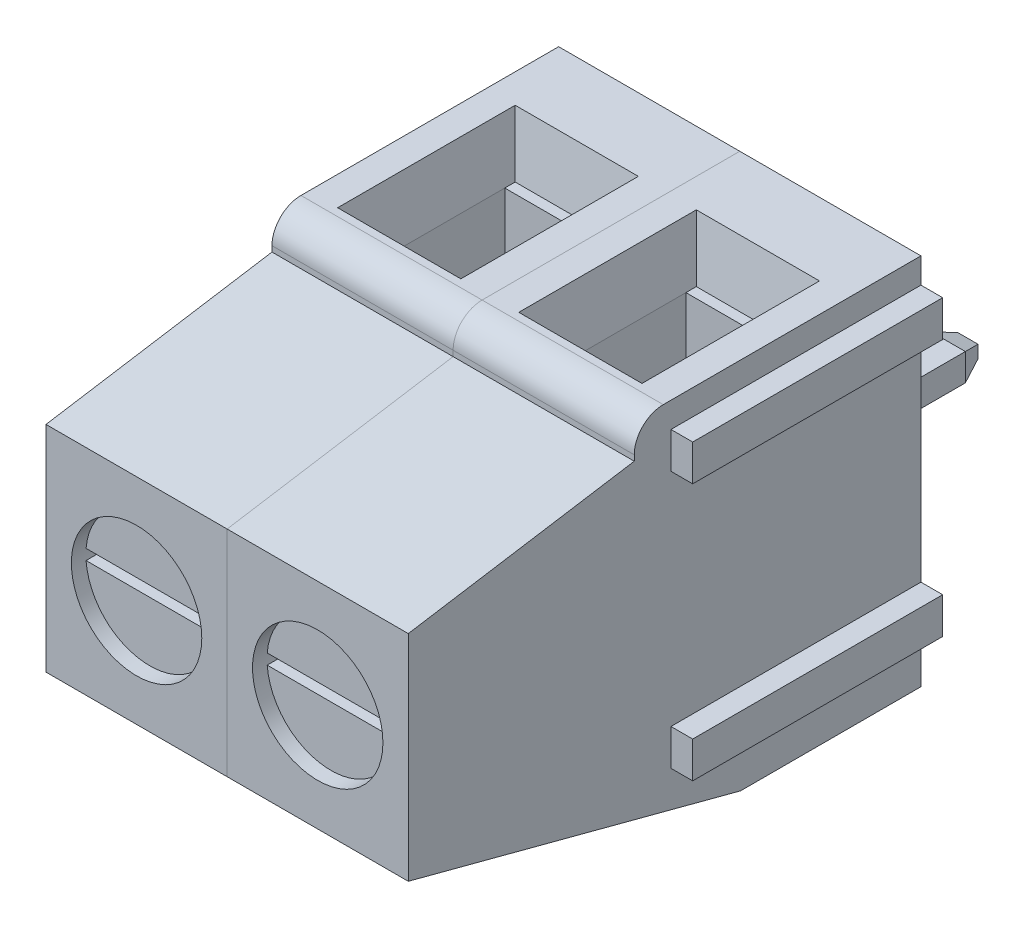
SolidWorks part; units mm, degrees
ref_plane "Спереди" through (0, 0, 0) normal (0, 0, 1) x (1, 0, 0)
ref_plane "Сверху" through (0, 0, 0) normal (0, 1, 0) x (1, 0, 0)
ref_plane "Справа" through (0, 0, 0) normal (1, 0, 0) x (0, 0, -1)
sketch "Эскиз3" plane through (0, 0, 0) normal (0, 0, 1) x (1, 0, 0)
  line L1 (-2.5, 5.3) -> (2.5, 5.3)
  line L2 (-2.5, 5.3) -> (-2.5, -5)
  line L3 (-2.5, -5) -> (2.5, -5)
  line L4 (2.5, 5.3) -> (2.5, -5)
  line L5 (-2.5, 5.3) -> (2.5, -5) construction
  line L6 (-2.5, -5) -> (2.5, 5.3) construction
  point P0 (0, 0.15)
  dimension "D1" = 10.3
  dimension "D2" = 5
  dimension "D3" = 5.3
extrude "Бобышка-Вытянуть2" add sketch "Эскиз3" along normal blind 14.15
sketch "Эскиз5" plane through (0, 0, 0) normal (0, 0, -1) x (-1, 0, 0)
  line L0 (-2.5, 5.3) -> (2.5, 5.3) construction
  line L1 (-1.5, 3.74) -> (1.5, 3.74)
  line L2 (-1.5, 3.74) -> (-1.5, -3.74)
  line L4 (1.5, 3.74) -> (1.5, -3.74)
  line L5 (-1.5, 3.74) -> (1.5, -3.74) construction
  line L6 (-1.5, -3.74) -> (1.5, 3.74) construction
  line L8 (2.5, -5) -> (-2.5, -5) construction
  line L10 (-1.5, -3.74) -> (-1.5, -4.14)
  line L11 (-1.5, -4.14) -> (1.5, -4.14)
  line L12 (1.5, -3.74) -> (1.5, -4.14)
  point P0 (0, 0)
  point P10 (0, -3.94)
  dimension "D1" = 3
  dimension "D2" = 1.56
  dimension "D3" = 0.86
extrude "Вырез-Вытянуть3" cut sketch "Эскиз5" against normal blind 6.9
sketch "Эскиз6" plane through (2.5, 0, 0) normal (1, 0, 0) x (0, 0, -1)
  line L0 (-80.2628, -91.3523) -> (-80.2628, -14.0189) construction
  line L1 (-4.9782, -5) -> (-14.15, -2.5764)
  line L2 (-14.15, -5) -> (0, -5) construction
  line L3 (-14.15, -5) -> (-14.15, 5.3) construction
  line L4 (-14.15, -2.5764) -> (-14.15, -5)
  line L5 (-14.15, -5) -> (-4.9782, -5)
  line L6 (-7.1129, 5.3) -> (-14.15, 5.3)
  line L7 (-14.15, 5.3) -> (0, 5.3) construction
  line L8 (-7.9129, 4.5) -> (-7.9129, 4.3474)
  line L9 (-7.9129, 4.3474) -> (-14.15, 3.3455)
  line L10 (-14.15, 3.3455) -> (-14.15, 5.3)
  arc A0 (-7.1129, 5.3) -> (-7.9129, 4.5) centre (-7.1129, 4.5) ccw
  point P20 (-7.9129, 5.3)
  dimension "D1" = 0.8
extrude "Вырез-Вытянуть4" cut sketch "Эскиз6" against normal through all
sketch "Эскиз7" plane through (0, 5.3, 0) normal (0, 1, 0) x (1, 0, 0)
  line L0 (2.5, -7.1129) -> (-2.5, 0) construction
  line L1 (2.5, 0) -> (-2.5, -7.1129) construction
  line L2 (-2.5, -7.1129) -> (-2.5, 0) construction
  line L3 (1.7, -6.9) -> (-1.7, -6.9)
  line L4 (1.7, -6.9) -> (1.7, -2)
  line L5 (1.7, -2) -> (-1.7, -2)
  line L6 (-1.7, -6.9) -> (-1.7, -2)
  line L7 (1.7, -6.9) -> (-1.7, -2) construction
  line L8 (1.7, -2) -> (-1.7, -6.9) construction
  line L10 (2.5, -7.1129) -> (2.5, 0) construction
  line L11 (2.5, 0) -> (-2.5, 0) construction
  point P8 (0, -4.45)
  dimension "D1" = 0.8
  dimension "D2" = 0.8
  dimension "D3" = 2
  dimension "D4" = 4.9
extrude "Вырез-Вытянуть5" cut sketch "Эскиз7" against normal blind 1.6 draft 10
sketch "Эскиз9" plane through (0, 5.3, 0) normal (0, 1, 0) x (1, 0, 0)
  line L0 (-1.7, -6.9) -> (-2.5, -6.9)
  line L1 (-2.5, -7.1129) -> (-2.5, 0) construction
  point P6 (-2.5, -6.9)
sketch "Эскиз10" plane through (-2.5, 0, 0) normal (-1, 0, 0) x (0, 0, 1)
  line L0 (6.9, 5.3) -> (5.5574, 3.7)
  line L1 (5.5574, 3.7) -> (6.9, 3.7)
  line L2 (6.9, 3.7) -> (6.9, 5.3)
  dimension "D1" = 1.6
  dimension "D2" = 40
extrude "Бобышка-Вытянуть3" add sketch "Эскиз10" against normal blind 4.6
sketch "Эскиз11" plane through (0, 0, 0) normal (0, 0, 1) x (1, 0, 0)
  line L0 (-2.5, -5) -> (2.5, -5) construction
  line L1 (-1, -3.7) -> (1, -3.7)
  line L2 (-1, -3.7) -> (-1, -5)
  line L3 (-1, -5) -> (1, -5)
  line L4 (1, -3.7) -> (1, -5)
  line L5 (-1, -3.7) -> (1, -5) construction
  line L6 (-1, -5) -> (1, -3.7) construction
  line L7 (0, 0) -> (0, -5) construction
  point P0 (0, -4.35)
  dimension "D1" = 2
  dimension "D2" = 1.3
extrude "Вырез-Вытянуть6" cut sketch "Эскиз11" along normal through all from offset 5
sketch "Эскиз13" plane through (-1, 0, 0) normal (1, 0, 0) x (0, 0, -1)
  line L0 (-6.9, -3.7) -> (-6.99, -4.2064)
  line L1 (-6.99, -4.2064) -> (-5, -4.3475)
  line L2 (-5, -4.14) -> (-5, -4.9942) construction
  line L3 (-5, -4.3475) -> (-5, -4.14)
  line L4 (-5, -4.14) -> (-6.9, -3.7)
extrude "Бобышка-Вытянуть6" add sketch "Эскиз13" against normal up to surface (0.5 mm away) up to face at (-1.5, 1.1, 4.1581)
sketch "Эскиз14" plane through (1, 0, 0) normal (-1, 0, 0) x (0, 0, 1)
  line L0 (6.9, -3.7) -> (5, -4.14)
  line L1 (6.9, -4.14) -> (6.9, -3.7) construction
  line L2 (9.8979, -3.7) -> (6.9, -3.7) construction
  line L3 (5, -4.14) -> (5, -4.475)
  line L4 (5, -4.9942) -> (5, -4.14) construction
  line L5 (5, -4.475) -> (7.0407, -4.3075)
  line L6 (7.0407, -4.3075) -> (6.9, -3.7)
extrude "Бобышка-Вытянуть7" add sketch "Эскиз14" against normal up to surface (0.5 mm away) up to face at (1.5, 1.1, 4.1581)
sketch "Эскиз15" plane through (0, 0, 14.15) normal (0, 0, 1) x (1, 0, 0)
  line L1 (2.5, -2.5764) -> (-2.5, -2.5764) construction
  line L2 (2.5, -2.5764) -> (2.5, 3.3455) construction
  line L3 (2.5, 3.3455) -> (-2.5, 3.3455) construction
  line L4 (-2.5, -2.5764) -> (-2.5, 3.3455) construction
  line L5 (2.5, -2.5764) -> (-2.5, 3.3455) construction
  line L6 (2.5, 3.3455) -> (-2.5, -2.5764) construction
  circle A0 centre (0, 0.3846) radius 1.8
  point P4 (0, 0.3846)
extrude "Вырез-Вытянуть7" cut sketch "Эскиз15" against normal blind 1.5
sketch "Эскиз16" plane through (0, 0, 12.65) normal (0, 0, 1) x (1, 0, 0)
  circle A0 centre (0, 0.3846) radius 1.75
extrude "Бобышка-Вытянуть8" add sketch "Эскиз16" along normal blind 0.5 separate body
sketch "Эскиз17" plane through (0, 0, 13.15) normal (0, 0, 1) x (1, 0, 0)
  line L1 (1.7445, 0.5356) -> (-1.8107, 0.5356)
  line L3 (1.7445, 0.2445) -> (-1.8107, 0.2445)
  arc A0 (1.7445, 0.5356) -> (-1.8107, 0.5356) centre (-0.0331, 0.39) ccw
  arc A1 (-1.8107, 0.2445) -> (1.7445, 0.2445) centre (-0.0331, 0.39) ccw
extrude "Бобышка-Вытянуть9" add sketch "Эскиз17" along normal blind 0.6
sketch "Эскиз18" plane through (0, 0, 0) normal (0, 0, -1) x (-1, 0, 0)
  line L1 (-2.5, 4.6) -> (-3.1, 4.6)
  line L2 (-2.5, 4.6) -> (-2.5, 3.6)
  line L3 (-2.5, 3.6) -> (-3.1, 3.6)
  line L4 (-3.1, 4.6) -> (-3.1, 3.6)
  line L5 (-2.5, 4.6) -> (-3.1, 3.6) construction
  line L6 (-2.5, 3.6) -> (-3.1, 4.6) construction
  line L7 (-2.5, 5.3) -> (2.5, 5.3) construction
  line L9 (-2.5, -3.5) -> (-3.1, -3.5)
  line L10 (-2.5, -3.5) -> (-2.5, -2.5)
  line L11 (-2.5, -2.5) -> (-3.1, -2.5)
  line L12 (-3.1, -3.5) -> (-3.1, -2.5)
  line L13 (-2.5, -3.5) -> (-3.1, -2.5) construction
  line L14 (-2.5, -2.5) -> (-3.1, -3.5) construction
  line L15 (2.5, -5) -> (-2.5, -5) construction
  point P4 (-2.8, 4.1)
  point P12 (-2.8, -3)
  dimension "D1" = 1
  dimension "D2" = 0.6
  dimension "D3" = 0.7
  dimension "D4" = 1
  dimension "D5" = 0.6
  dimension "D6" = 1.5
extrude "Бобышка-Вытянуть10" add sketch "Эскиз18" against normal blind 6.9
sketch "Эскиз19" plane through (0, 0, 0) normal (0, 0, -1) x (-1, 0, 0)
  line L0 (2.5, 5.3) -> (2.5, -5) construction
  line L1 (2.5, 4.6) -> (1.9, 4.6)
  line L2 (2.5, 4.6) -> (2.5, 3.6)
  line L3 (2.5, 3.6) -> (1.9, 3.6)
  line L4 (1.9, 4.6) -> (1.9, 3.6)
  line L5 (2.5, 4.6) -> (1.9, 3.6) construction
  line L6 (2.5, 3.6) -> (1.9, 4.6) construction
  line L7 (2.5, -5) -> (-2.5, -5) construction
  line L8 (2.5, -2.5) -> (1.9, -2.5)
  line L9 (2.5, -2.5) -> (2.5, -3.5)
  line L10 (2.5, -3.5) -> (1.9, -3.5)
  line L11 (1.9, -2.5) -> (1.9, -3.5)
  line L12 (2.5, -2.5) -> (1.9, -3.5) construction
  line L13 (2.5, -3.5) -> (1.9, -2.5) construction
  point P4 (2.2, 4.1)
  point P11 (2.2, -3)
  dimension "D1" = 0.6
  dimension "D2" = 0.6
  dimension "D3" = 1
  dimension "D4" = 1
  dimension "D5" = 1.5
extrude "Вырез-Вытянуть8" cut sketch "Эскиз19" against normal blind 6.9
sketch "Эскиз20" plane through (1.5, 0, 0) normal (-1, 0, 0) x (0, 0, 1)
  line L0 (6.9, -3.7) -> (0.8163, -3.7)
  line L1 (0.8163, -3.7) -> (0.8163, 0.4782)
  line L2 (0.8163, 0.4782) -> (1.1919, 0.4782)
  line L3 (1.1919, 0.4782) -> (1.1919, -3.3823)
  line L4 (1.1919, -3.3823) -> (7.0251, -3.3823)
  line L5 (7.0251, -3.3823) -> (6.9, -3.7)
extrude "Бобышка-Вытянуть11" add sketch "Эскиз20" along normal up to surface (3 mm away) separate body up to face at (-1.5, 0.4143, 4.2783)
sketch "Эскиз21" plane through (0, 0, 0.8163) normal (0, 0, -1) x (-1, 0, 0)
  line L0 (1.2161, -3.0918) -> (1.5, -3.0918)
  line L2 (1.2161, 0.4782) -> (1.2161, -3.0918)
  line L4 (-1.2161, 0.4782) -> (-1.2161, -3.0918)
  line L7 (1.5, 0.4782) -> (1.5, -3.7) construction
  line L8 (1.5, -3.0918) -> (1.5, 0.4782)
  line L9 (1.5, 0.4782) -> (1.2161, 0.4782)
  line L10 (1.5, 0.4782) -> (-1.5, 0.4782) construction
  line L11 (-1.5, 0.4782) -> (-1.2161, 0.4782)
  line L12 (-1.5, 0.4782) -> (-1.5, -3.0918)
  line L13 (-1.5, -3.0918) -> (-1.2161, -3.0918)
  point P0 (0, 0)
extrude "Вырез-Вытянуть9" cut sketch "Эскиз21" against normal blind 1.9
sketch "Эскиз22" plane through (0, 3.74, 0) normal (0, -1, 0) x (-1, 0, 0)
  line L0 (-1.5, -5.591) -> (-1.5, 0) construction
  line L1 (-1.5, -2.0403) -> (1.5, -2.0403)
  line L2 (-1.5, -2.0403) -> (-1.5, -5.8511)
  line L3 (-1.5, -5.8511) -> (1.5, -5.8511)
  line L4 (1.5, -2.0403) -> (1.5, -5.8511)
  line L5 (-1.5, -2.0403) -> (1.5, -5.8511) construction
  line L6 (-1.5, -5.8511) -> (1.5, -2.0403) construction
  point P4 (0, -3.9457)
extrude "Бобышка-Вытянуть12" add sketch "Эскиз22" along normal blind 5.9 separate body
sketch "Эскиз23" plane through (0, 3.74, 0) normal (0, 1, 0) x (1, 0, 0)
  line L0 (-1.4249, -2.2751) -> (-1.4249, -5.591) construction
  line L1 (-1.4249, -2.562) -> (1.4249, -2.562)
  line L2 (-1.4249, -2.562) -> (-1.4249, -5.4379)
  line L3 (-1.4249, -5.4379) -> (1.4249, -5.4379)
  line L4 (1.4249, -2.562) -> (1.4249, -5.4379)
  line L5 (-1.4249, -2.562) -> (1.4249, -5.4379) construction
  line L6 (-1.4249, -5.4379) -> (1.4249, -2.562) construction
  line L7 (1.4249, -5.591) -> (1.4249, -2.2751) construction
  point P4 (0, -4)
extrude "Вырез-Вытянуть10" cut sketch "Эскиз23" against normal blind 5.9
sketch "Эскиз24" plane through (0, 0, 0) normal (0, 0, 1) x (1, 0, 0)
  line L1 (0.475, 0.375) -> (-0.475, 0.375)
  line L2 (0.475, 0.375) -> (0.475, -0.375)
  line L3 (0.475, -0.375) -> (-0.475, -0.375)
  line L4 (-0.475, 0.375) -> (-0.475, -0.375)
  line L5 (0.475, 0.375) -> (-0.475, -0.375) construction
  line L6 (0.475, -0.375) -> (-0.475, 0.375) construction
  point P0 (0, 0)
  dimension "D1" = 0.95
  dimension "D2" = 0.75
extrude "Бобышка-Вытянуть13" add sketch "Эскиз24" along normal up to surface (0.8163 mm away) and the other way blind 3.8 separate body up to face at (0, -2.3514, 0.8163)
chamfer "Фаска1" distance 0.2 angle 70 4 edges at (0, -0.375, -3.8) (0.475, 0, -3.8) (0, 0.375, -3.8) (-0.475, 0, -3.8) first distance on face at (0, 0, -3.8)
pattern_linear "Линейный массив1" count 2 spacing 5 along (1, 0, 0) of bodies 122 133 132 130
